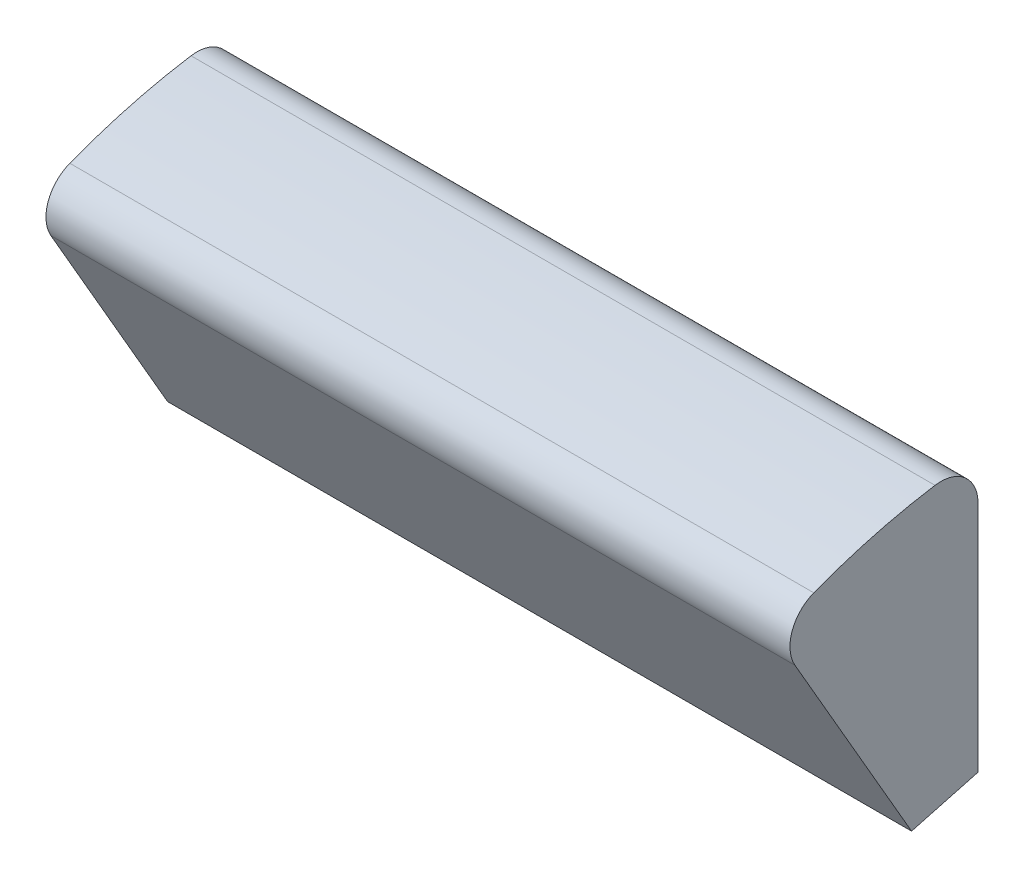
SolidWorks part; units mm, degrees
ref_plane "Front Plane" through (0, 0, 0) normal (0, 0, 1) x (1, 0, 0)
ref_plane "Top Plane" through (0, 0, 0) normal (0, 1, 0) x (1, 0, 0)
ref_plane "Right Plane" through (0, 0, 0) normal (1, 0, 0) x (0, 0, -1)
sketch "Sketch3" plane through (0, 0, 0) normal (1, 0, 0) x (0, 0, -1)
  line L0 (-14.25, 24.6817) -> (-5.575, 9.6562) construction
  line L1 (0, 28.5) -> (0, 11.15) construction
  line L2 (-1.5, 22.2261) -> (-1.5, 12.8219) construction
  line L3 (-9.814, 19.9984) -> (-5.1119, 11.8541) construction
  line L4 (-1.5, 12.8219) -> (-2.4142, 11.9077) construction
  line L5 (-2.4142, 11.9077) -> (-2.1549, 10.9398) construction
  line L6 (-3.6037, 10.5516) -> (-3.8631, 11.5195) construction
  line L7 (-3.8631, 11.5195) -> (-5.1119, 11.8541) construction
  line L8 (0, 0) -> (-6.4601, 24.1093) construction
  line L9 (-2, 22.2261) -> (-2, 12.8219)
  line L10 (-9.381, 20.2484) -> (-4.6789, 12.1041)
  line L11 (-4.6789, 12.1041) -> (-2, 12.8219)
  arc A0 (0, 28.5) -> (-14.25, 24.6817) centre (0, 0) ccw construction
  arc A1 (0, 11.15) -> (-5.575, 9.6562) centre (0, 0) ccw construction
  arc A2 (-8.8004, 22.8649) -> (-3.8111, 24.2018) centre (0, 0) cw construction
  arc A3 (-5.575, 9.6562) -> (-3.6037, 10.5516) centre (0, 0) cw construction
  arc A4 (-2.1549, 10.9398) -> (0, 11.15) centre (0, 0) cw construction
  arc A5 (-1.5, 22.2261) -> (-3.8111, 24.2018) centre (-3.5, 22.2261) ccw construction
  arc A6 (-8.8004, 22.8649) -> (-9.814, 19.9984) centre (-8.082, 20.9984) ccw construction
  arc A7 (-2.4142, 11.9077) -> (-3.8631, 11.5195) centre (0, 0) ccw construction
  arc A8 (-2, 22.2261) -> (-3.7333, 23.7079) centre (-3.5, 22.2261) ccw
  arc A9 (-8.6208, 22.3983) -> (-3.7333, 23.7079) centre (0, 0) cw
  arc A10 (-8.6208, 22.3983) -> (-9.381, 20.2484) centre (-8.082, 20.9984) ccw
  dimension "D1" = 28.5
  dimension "D2" = 11.15
  dimension "D7" = 2
  dimension "D3" = 30
  dimension "D4" = 1.5
  dimension "D5" = 1.5
  dimension "D6" = 4
  dimension "D8" = 15
  dimension "D9" = 1.5
  dimension "D10" = 0.75
  dimension "D11" = 1
  dimension "D12" = 120
  dimension "D13" = 120
  dimension "D14" = 0.5
extrude "Boss-Extrude1" add sketch "Sketch3" along normal blind 30
ref_axis "Axis1" through (-2, 0, 0) along (1, 0, 0)
equation "\"OuterDiam\" = 57"
equation "\"InnerDiam\"= 22.3"
equation "\"Length\"= 30"
equation "\"slots\"= 12"
equation "\"ppairs\"= 2"
equation "\"hYoke\"= 4"
equation "\"wTooth\" = 3"
equation "\"D1@Sketch3\"=\"OuterDiam\"/2"
equation "\"D2@Sketch3\"=\"InnerDiam\"/2"
equation "\"D3@Sketch3\"=360deg/\"slots\""
equation "\"D5@Sketch3\"=\"wTooth\"/2"
equation "\"D4@Sketch3\"=\"wTooth\"/2"
equation "\"D6@Sketch3\"=\"hYoke\""
equation "\"D1@Boss-Extrude1\"=\"Length\""
equation "\"D8@Sketch3\"= 360deg / \"slots\" / 2"
equation "\"D10@Sketch3\"=\"D9@Sketch3\"/2"
equation "\"D13@Sketch3\"=\"D12@Sketch3\""
